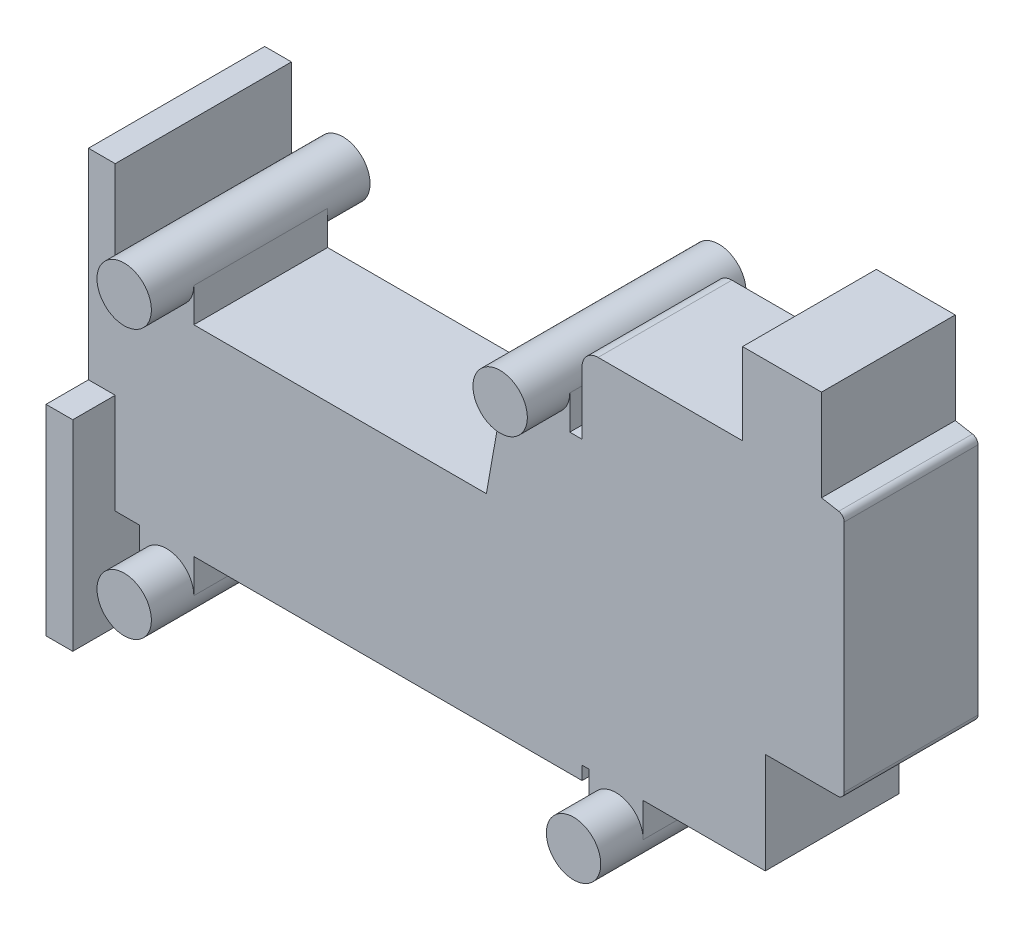
SolidWorks part; units mm, degrees
ref_plane "Front Plane" through (0, 0, 0) normal (0, 0, 1) x (1, 0, 0)
ref_plane "Top Plane" through (0, 0, 0) normal (0, 1, 0) x (1, 0, 0)
ref_plane "Right Plane" through (0, 0, 0) normal (1, 0, 0) x (0, 0, -1)
sketch "Sketch1" plane through (0, 0, 0) normal (0, 0, 1) x (1, 0, 0)
  line L1 (-12.7, 7.5) -> (12.7, 7.5)
  line L2 (-12.7, 7.5) -> (-12.7, -7.5)
  line L3 (-12.7, -7.5) -> (12.7, -7.5)
  line L4 (12.7, 7.5) -> (12.7, -7.5)
  line L5 (-12.7, 7.5) -> (12.7, -7.5) construction
  line L6 (-12.7, -7.5) -> (12.7, 7.5) construction
  point P0 (0, 0)
  dimension "D1" = 25.4
  dimension "D2" = 15
extrude "Boss-Extrude1" add sketch "Sketch1" along normal blind 10
sketch "Sketch2" plane through (0, 0, 10) normal (0, 0, 1) x (1, 0, 0)
  line L0 (35.9, 20.5) -> (40.97, 19.606) construction
  line L1 (41.3868, 19.5325) -> (40.97, 19.606) construction
  line L2 (41.8, 1.55) -> (41.8, 19.0401) construction
  line L3 (40.1, 19.7594) -> (40.1, 26.6) construction
  line L4 (40.1, 26.6) -> (34.2, 26.6) construction
  line L5 (34.2, 26.6) -> (34.2, 20.5) construction
  line L6 (23.4, 20.5) -> (34.7, 20.5) construction
  line L7 (22.2, 3.5) -> (22.2, 19.3) construction
  line L8 (16.3, 14.6) -> (22.2, 14.6) construction
  line L9 (16.3, 14.6) -> (15.048, 7.5) construction
  line L10 (9.4, 7.5) -> (15.048, 7.5) construction
  line L11 (40.1, 19.7594) -> (40.97, 19.606)
  line L12 (41.3868, 19.5325) -> (40.97, 19.606)
  line L13 (41.8, 1.55) -> (41.8, 19.0401)
  line L14 (40.1, 19.7594) -> (40.1, 26.6)
  line L15 (40.1, 26.6) -> (34.2, 26.6)
  line L16 (34.2, 26.6) -> (34.2, 20.5)
  line L17 (23.4, 20.5) -> (34.2, 20.5)
  line L18 (22.2, 14.6) -> (22.2, 19.3)
  line L19 (16.3, 14.6) -> (22.2, 14.6)
  line L20 (16.3, 14.6) -> (15.048, 7.5)
  line L21 (9.4, 7.5) -> (15.048, 7.5)
  line L22 (40.8832, 1.05) -> (35.9, 1.05) construction
  line L23 (40.8832, 1.05) -> (41.3, 1.05) construction
  line L24 (40.8832, 1.05) -> (35.9, 1.05)
  line L25 (40.8832, 1.05) -> (41.3, 1.05)
  line L26 (35.9, -2.35) -> (35.9, 1.05) construction
  line L27 (35.9, -2.35) -> (35.9, 1.05)
  line L28 (9.4, -7.5) -> (22.2, -7.5) construction
  line L29 (22.2, 14.6) -> (22.2, -7.5) construction
  line L30 (35.9, -2.35) -> (35.9, -6.5) construction
  line L31 (34.9, -6.5) -> (35.9, -6.5) construction
  line L32 (34.9, -6.5) -> (22.2, -6.5) construction
  line L33 (9.4, -7.5) -> (22.2, -7.5)
  line L34 (22.2, -6.5) -> (22.2, -7.5)
  line L35 (35.9, -2.35) -> (35.9, -6.5)
  line L36 (34.9, -6.5) -> (35.9, -6.5)
  line L37 (34.9, -6.5) -> (22.2, -6.5)
  line L38 (9.4, -7.5) -> (9.4, 7.5)
  line L41 (-12.7, 11) -> (-12.7, 14.2) construction
  line L42 (-12.7, 7.5) -> (-12.7, 12.7105) construction
  line L43 (-14.7, 14.2) -> (-14.7, 14.9937)
  line L44 (-12.7, -14.2) -> (-12.7, -10.0691) construction
  line L45 (-14.7, -10.0691) -> (-14.7, -14.2) construction
  line L46 (-14.7, -10.0691) -> (-14.7, 0) construction
  line L47 (-14.7, 0) -> (-14.7, 7.5) construction
  line L48 (-14.7, 7.5) -> (-14.7, 12.7105) construction
  line L49 (-14.7, 14.2) -> (-14.7, 11) construction
  line L50 (-12.7, 12.7105) -> (-12.7, 14.2)
  line L51 (-12.7, 7.5) -> (-12.7, 12.7105)
  line L52 (-12.7, 0) -> (-12.7, 7.5)
  line L53 (-12.7, -14.2) -> (-12.7, -10.0691)
  line L54 (-14.7, -10.0691) -> (-14.7, -14.2)
  line L55 (-14.7, -10.0691) -> (-14.7, 0)
  line L56 (-14.7, 0) -> (-14.7, 7.5)
  line L57 (-14.7, 7.5) -> (-14.7, 11)
  line L58 (-14.7, 14.2) -> (-14.7, 11)
  line L59 (-12.7, -10.0691) -> (-12.7, 0) construction
  line L61 (-12.7, -10.0691) -> (-12.7, 0)
  line L63 (-14.7, 14.9937) -> (-12.7, 14.9937)
  line L64 (-12.7, 14.9937) -> (-12.7, 14.2)
  line L65 (-14.7, -14.2) -> (-14.7, -14.9938)
  line L66 (-14.7, -14.9938) -> (-12.7, -14.9938)
  line L67 (-12.7, -14.9938) -> (-12.7, -14.2)
  arc A0 (41.8, 19.0401) -> (41.3868, 19.5325) centre (41.3, 19.0401) ccw construction
  arc A1 (23.4, 20.5) -> (22.2, 19.3) centre (23.4, 19.3) ccw construction
  arc A2 (41.8, 19.0401) -> (41.3868, 19.5325) centre (41.3, 19.0401) ccw
  arc A3 (23.4, 20.5) -> (22.2, 19.3) centre (23.4, 19.3) ccw
  arc A4 (41.3, 1.05) -> (41.8, 1.55) centre (41.3, 1.55) ccw construction
  arc A5 (41.3, 1.05) -> (41.8, 1.55) centre (41.3, 1.55) ccw
  dimension "D1" = 0.7937
extrude "Boss-Extrude2" add sketch "Sketch2" against normal up to surface (10 mm away) up to face at (0, 0, 0)
sketch "Sketch3" plane through (-14.7, 0, 0) normal (-1, 0, 0) x (0, 0, 1)
  line L0 (0, 14.9937) -> (-3.175, 14.9937)
  line L1 (-3.175, 14.9937) -> (-3.175, 0)
  line L2 (-3.175, 0) -> (0, 0)
  line L3 (0, -14.9938) -> (0, 14.9937) construction
  line L4 (0, 0) -> (0, 14.9937)
  line L5 (10, 14.9937) -> (10, -14.9938) construction
  line L6 (10, 0) -> (13.175, 0)
  line L7 (10, 0) -> (10, -14.9938)
  line L8 (10, -14.9938) -> (13.175, -14.9938)
  line L9 (13.175, 0) -> (13.175, -14.9938)
  dimension "D1" = 3.175
extrude "Boss-Extrude3" add sketch "Sketch3" against normal up to surface (2 mm away) up to face at (-12.7, 11.2469, 5)
sketch "Sketch4" plane through (0, 0, 10) normal (0, 0, 1) x (1, 0, 0)
  line L0 (9.61, 7.5) -> (15.048, 7.5) construction
  line L1 (15.048, 7.5) -> (-12.7, 7.5) construction
  line L2 (9.61, 7.5) -> (9.61, 12.2625) construction
  line L3 (12.329, 7.5) -> (12.329, 10.04) construction
  line L4 (10.297, 7.5) -> (10.297, 10.04)
  line L5 (14.361, 7.5) -> (14.361, 10.04)
  line L6 (0, 0) -> (35.9, 0) construction
  line L7 (35.9, -6.5) -> (35.9, 1.05) construction
  line L8 (9.61, -7.5) -> (15.048, -7.5) construction
  line L9 (12.329, -7.5) -> (12.329, -10.04) construction
  line L10 (10.297, -7.5) -> (10.297, -10.04)
  line L11 (14.361, -7.5) -> (14.361, -10.04)
  arc A0 (10.297, 7.5) -> (14.361, 7.5) centre (12.329, 7.5) ccw
  arc A1 (14.361, 10.04) -> (10.297, 10.04) centre (12.329, 10.04) ccw
  arc A2 (10.297, -7.5) -> (14.361, -7.5) centre (12.329, -7.5) cw
  arc A3 (14.361, -10.04) -> (10.297, -10.04) centre (12.329, -10.04) cw
  point P9 (12.329, 8.77)
  point P23 (12.329, -8.77)
  dimension "D1" = 2.032
  dimension "D2" = 2.54
extrude "Boss-Extrude4" [suppressed] add sketch "Sketch4" against normal up to surface (10 mm away) up to face at (19.5643, 7.0398, 0)
sketch "Sketch5" [suppressed] plane through (0, 0, 0) normal (0, 0, -1) x (-1, 0, 0)
  circle A0 centre (-12.329, 10.04) radius 2.032
  circle A1 centre (-12.329, -10.04) radius 2.032
  arc A2 (-14.361, -10.04) -> (-10.297, -10.04) centre (-12.329, -10.04) ccw construction
  arc A3 (-10.297, 10.04) -> (-14.361, 10.04) centre (-12.329, 10.04) ccw construction
extrude "Boss-Extrude5" [suppressed] add sketch "Sketch5" along normal blind 3.175 and the other way blind 13.175
sketch "Sketch6" plane through (0, 0, 10) normal (0, 0, 1) x (1, 0, 0)
  line L0 (-5.01, 7.5) -> (-12.7, 7.5) construction
  line L1 (-5.01, 12.2625) -> (-5.01, 7.5) construction
  line L2 (10.297, 7.5) -> (-12.7, 7.5) construction
  line L3 (-8.855, 7.5) -> (-8.855, 10.04) construction
  line L4 (-10.887, 7.5) -> (-10.887, 10.04)
  line L5 (-6.823, 7.5) -> (-6.823, 10.04)
  line L6 (-12.7, 0) -> (0, 0) construction
  line L7 (-8.855, -7.5) -> (-8.855, -10.04) construction
  line L8 (-10.887, -7.5) -> (-10.887, -10.04)
  line L9 (-6.823, -7.5) -> (-6.823, -10.04)
  line L10 (19.25, 14.6) -> (19.25, 17.14) construction
  line L14 (22.2, 14.6) -> (16.3, 14.6) construction
  line L18 (17.218, 14.6) -> (17.218, 17.14)
  line L19 (21.282, 14.6) -> (21.282, 17.14)
  line L20 (22.2, -6.5) -> (27.28, -6.5) construction
  line L21 (22.2, -6.5) -> (35.9, -6.5) construction
  line L22 (24.74, -6.5) -> (24.74, -9.04) construction
  line L23 (26.772, -6.5) -> (26.772, -9.04)
  line L24 (22.708, -6.5) -> (22.708, -9.04)
  arc A0 (-10.887, 7.5) -> (-6.823, 7.5) centre (-8.855, 7.5) ccw
  arc A1 (-6.823, 10.04) -> (-10.887, 10.04) centre (-8.855, 10.04) ccw
  arc A2 (-10.887, -7.5) -> (-6.823, -7.5) centre (-8.855, -7.5) cw
  arc A3 (-6.823, -10.04) -> (-10.887, -10.04) centre (-8.855, -10.04) cw
  arc A10 (17.218, 14.6) -> (21.282, 14.6) centre (19.25, 14.6) ccw
  arc A11 (21.282, 17.14) -> (17.218, 17.14) centre (19.25, 17.14) ccw
  arc A12 (26.772, -6.5) -> (22.708, -6.5) centre (24.74, -6.5) ccw
  arc A13 (22.708, -9.04) -> (26.772, -9.04) centre (24.74, -9.04) ccw
  point P9 (-8.855, 8.77)
  point P20 (-8.855, -8.77)
  point P29 (19.25, 15.87)
  point P40 (24.74, -7.77)
  dimension "D1" = 2.032
  dimension "D4" = 2.032
  dimension "D2" = 2.54
  dimension "D3" = 2.54
  dimension "D5" = 5.08
extrude "Boss-Extrude6" add sketch "Sketch6" against normal up to surface (10 mm away) up to face at (19.5643, 7.0398, 0)
sketch "Sketch7" plane through (0, 0, 0) normal (0, 0, -1) x (-1, 0, 0)
  circle A0 centre (-19.25, 17.14) radius 2.032
  circle A1 centre (-24.74, -9.04) radius 2.032
  circle A2 centre (8.855, -10.04) radius 2.032
  circle A3 centre (8.855, 10.04) radius 2.032
extrude "Boss-Extrude7" add sketch "Sketch7" along normal blind 3.175 and the other way blind 13.175
sketch "Sketch8" [suppressed] plane through (0, 14.9937, 0) normal (0, 1, 0) x (1, 0, 0)
  line L0 (-12.7, -13.175) -> (-14.7, -13.175) construction
  line L1 (-12.7, 0) -> (-14.7, 0)
  line L2 (-12.7, 0) -> (-12.7, 3.175)
  line L3 (-12.7, 3.175) -> (-14.7, 3.175)
  line L4 (-14.7, 0) -> (-14.7, 3.175)
  line L5 (-12.7, -10) -> (-14.7, -10)
  line L6 (-12.7, -10) -> (-12.7, -13.175)
  line L7 (-12.7, -13.175) -> (-14.7, -13.175)
  line L8 (-14.7, -10) -> (-14.7, -13.175)
extrude "Cut-Extrude1" [suppressed] cut sketch "Sketch8" against normal through all
